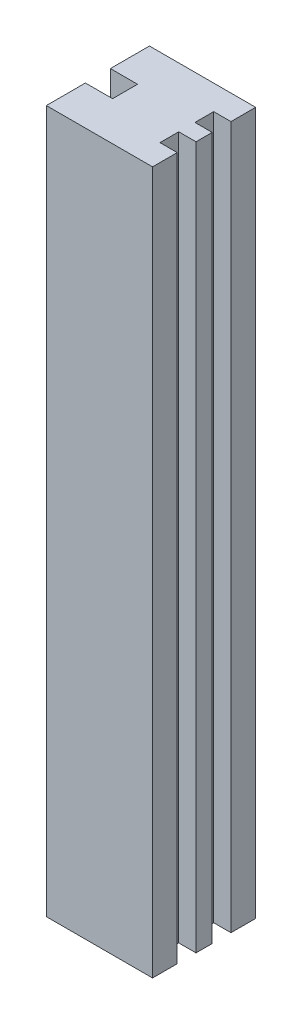
SolidWorks part; units mm, degrees
ref_plane "Спереди" through (0, 0, 0) normal (0, 0, 1) x (1, 0, 0)
ref_plane "Сверху" through (0, 0, 0) normal (0, 1, 0) x (1, 0, 0)
ref_plane "Справа" through (0, 0, 0) normal (1, 0, 0) x (0, 0, -1)
sketch "Эскиз1" plane through (0, 0, 0) normal (0, 1, 0) x (1, 0, 0)
  line L0 (0, 3.6577) -> (0, -3.6577)
  line L1 (0, -3.6577) -> (-7.957, -3.6577)
  line L2 (-7.957, -3.6577) -> (-7.957, -15.1002)
  line L3 (-7.957, -15.1002) -> (23.1476, -15.1002)
  line L4 (23.1476, -15.1002) -> (23.1476, -7.8666)
  line L5 (23.1476, -7.8666) -> (18.0908, -7.8666)
  line L6 (18.0908, -7.8666) -> (18.0908, -2.372)
  line L7 (-18.9883, 0) -> (46.2952, 0) construction
  line L8 (18.0908, -2.372) -> (23.1476, -2.372)
  line L9 (23.1476, -2.372) -> (23.1476, 2.372)
  line L10 (18.0908, 2.372) -> (23.1476, 2.372)
  line L11 (18.0908, 7.8666) -> (18.0908, 2.372)
  line L12 (23.1476, 7.8666) -> (18.0908, 7.8666)
  line L13 (23.1476, 15.1002) -> (23.1476, 7.8666)
  line L14 (-7.957, 15.1002) -> (23.1476, 15.1002)
  line L15 (-7.957, 3.6577) -> (-7.957, 15.1002)
  line L16 (0, 3.6577) -> (-7.957, 3.6577)
  point P14 (23.1476, 0)
  point P21 (0, 0)
extrude "Бобышка-Вытянуть1" add sketch "Эскиз1" along normal blind 205.74
